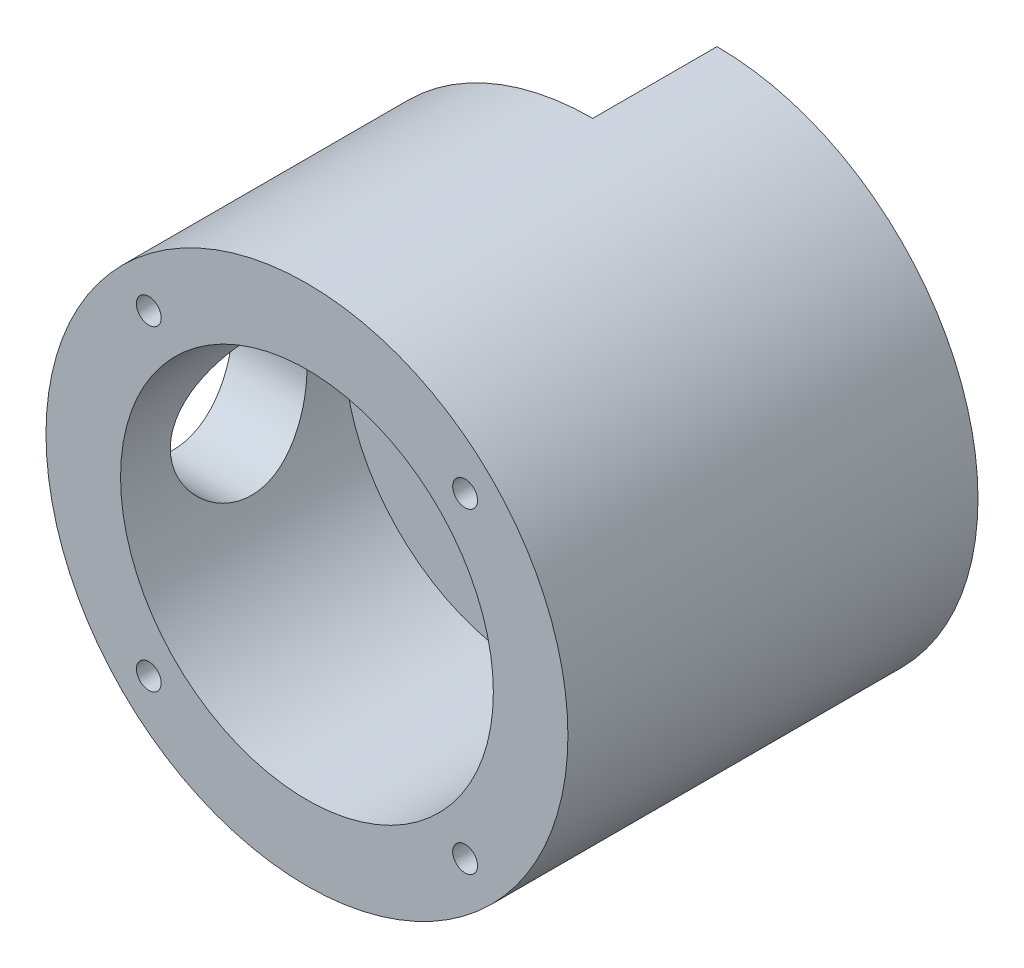
SolidWorks part; units mm, degrees
ref_plane "Front Plane" through (0, 0, 0) normal (0, 0, 1) x (1, 0, 0)
ref_plane "Top Plane" through (0, 0, 0) normal (0, 1, 0) x (1, 0, 0)
ref_plane "Right Plane" through (0, 0, 0) normal (1, 0, 0) x (0, 0, -1)
sketch "Sketch1" plane through (0, 0, 0) normal (0, 0, 1) x (1, 0, 0)
  circle A0 centre (0, 0) radius 10.5
  dimension "D1" = 21
extrude "Boss-Extrude1" add sketch "Sketch1" along normal blind 16.5
sketch "Sketch2" plane through (0, 0, 16.5) normal (0, 0, 1) x (1, 0, 0)
  circle A0 centre (0, 0) radius 7.5
  dimension "D1" = 15
extrude "Cut-Extrude1" cut sketch "Sketch2" against normal blind 9
sketch "Sketch15" plane through (0, 0, 16.5) normal (0, 0, 1) x (1, 0, 0)
  line L0 (0, 0) -> (12.0491, 0) construction
  line L1 (0, 0) -> (6.364, 6.364) construction
  circle A0 centre (0, 0) radius 9 construction
  circle A1 centre (6.364, 6.364) radius 0.5
  dimension "D1" = 18
  dimension "D3" = 1
  dimension "D2" = 45
extrude "Cut-Extrude10" cut sketch "Sketch15" against normal blind 3
pattern_circular "CirPattern1" count 4 over 360 about axis through (0, 0, 16.5) along (0, 0, -1) of "Cut-Extrude10"
sketch "Sketch9" plane through (0, 0, 0) normal (1, 0, 0) x (0, 0, -1)
  line L0 (0, 0) -> (-33.1355, 0) construction
  line L7 (-5, 0) -> (-5, 7.5)
  line L8 (-5, 7.5) -> (-2.5, 7.5)
  line L9 (-2.5, 7.5) -> (-2.5, 5.5)
  line L11 (-2.5, 5.5) -> (0, 5.5)
  line L12 (0, 5.5) -> (0, 0)
  line L14 (-5, 0) -> (0, 0)
  dimension "D1" = 2.5
  dimension "D2" = 5
  dimension "D3" = 5.5
  dimension "D4" = 7.5
revolve "Cut-Revolve1" cut sketch "Sketch9" angle 360 about L0
sketch "Sketch11" plane through (0, 0, 0) normal (1, 0, 0) x (0, 0, -1)
  line L0 (-16.5, 10.5) -> (-16.5, -10.5) construction
  circle A0 centre (-11.75, 0) radius 2.75
  dimension "D1" = 5.5
  dimension "D2" = 4.75
extrude "Cut-Extrude6" cut sketch "Sketch11" against normal through all
ref_axis "Axis1" through (0, 0, 16.5) along (0, 0, -1)
sketch "Sketch13" plane through (0, 0, 0) normal (1, 0, 0) x (0, 0, -1)
  line L0 (-16.5, -10.5) -> (0, -10.5) construction
  line L1 (0, 10.5) -> (-5, 10.5)
  line L2 (0, 10.5) -> (0, -10.5)
  line L3 (0, -10.5) -> (-5, -10.5)
  line L4 (-5, 10.5) -> (-5, -10.5)
  dimension "D1" = 5
extrude "Cut-Extrude8" cut sketch "Sketch13" against normal through all
sketch "Sketch14" plane through (0, 0, 0) normal (-1, 0, 0) x (0, 0, 1)
  line L0 (0, 5.5) -> (0, 10.5) construction
  line L1 (0, 10.5) -> (5, 10.5) construction
  circle A0 centre (2.5, 9) radius 0.5
  dimension "D1" = 1
  dimension "D2" = 2.5
  dimension "D3" = 1.5
extrude "Cut-Extrude9" cut sketch "Sketch14" against normal blind 2
mirror "Mirror1" about plane through (0, 0, 0) normal (0, 1, 0) of "Cut-Extrude9"
